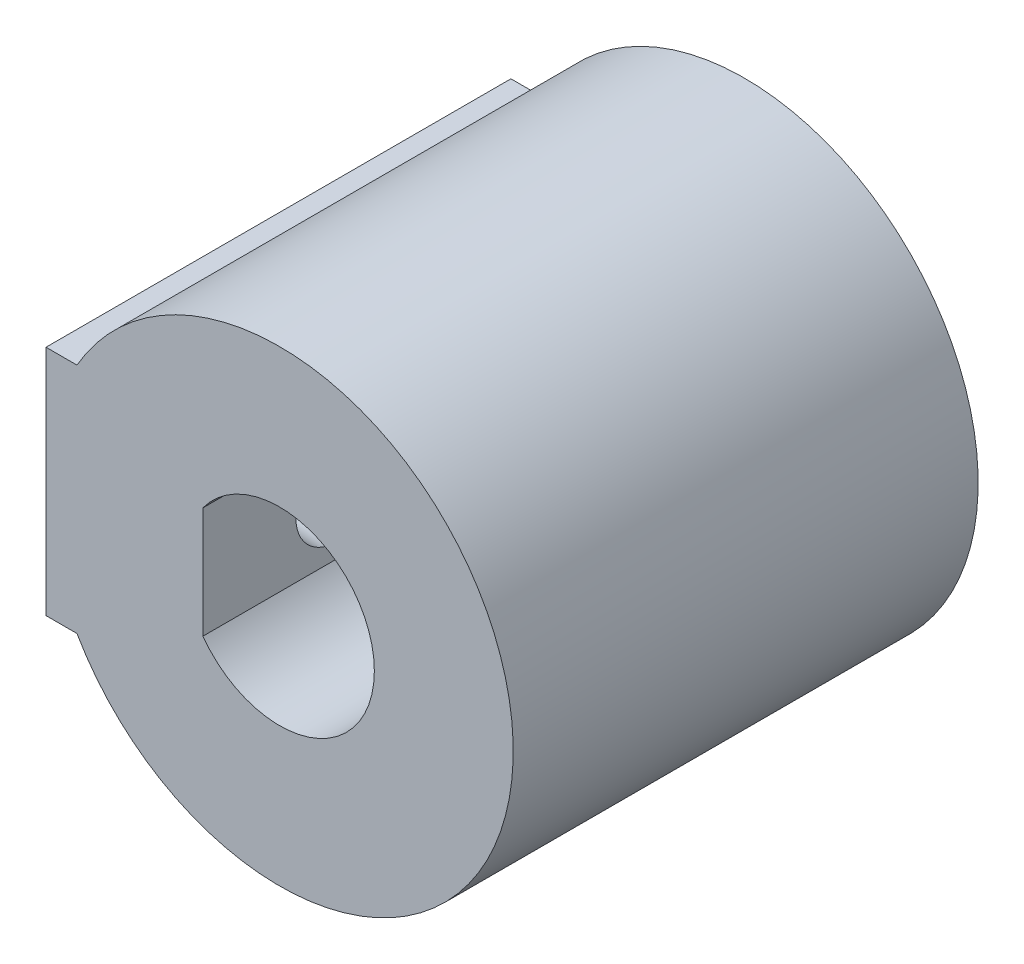
SolidWorks part; units mm, degrees
note: '?' marks a value the reader was unsure of.
ref_plane "Front Plane" through (0, 0, 0) normal (0, 0, 1) x (1, 0, 0)
ref_plane "Top Plane" through (0, 0, 0) normal (0, 1, 0) x (1, 0, 0)
ref_plane "Right Plane" through (0, 0, 0) normal (1, 0, 0) x (0, 0, -1)
sketch "Sketch1" plane through (0, 0, 0) normal (0, 0, 1) x (1, 0, 0)
  circle A0 centre (0, 0) radius 10.05
  dimension "D1" = 20.1
extrude "Boss-Extrude1" add sketch "Sketch1" along normal blind 20
ref_axis "Axis1" through (0, 0, 20) along (0, 0, -1)?
sketch "Sketch4" plane through (0, 0, 0) normal (0, 0, -1) x (-1, 0, 0)
  line L0 (-1.6, -2.1) -> (-1.6, 2.1)
  line L1 (1.6, 2.1) -> (1.6, -2.1)
  line L2 (-1.6, -2.1) -> (1.6, -2.1) construction
  line L3 (-1.6, 2.1) -> (1.6, 2.1) construction
  arc A0 (-1.6, 2.1) -> (1.6, 2.1) centre (0, -0.0749) cw
  arc A1 (1.6, -2.1) -> (-1.6, -2.1) centre (0, 0.0749) cw
  point P6 (-1.6, 0)
  point P7 (0, -2.1)
  point P8 (1.6, 0)
  point P10 (0, 2.1)
  dimension "D3" = 2.7
  dimension "D4" = 2.7
  dimension "D1" = 4.2
  dimension "D2" = 3.2
extrude "Cut-Extrude2" cut sketch "Sketch4" against normal blind 8.5
sketch "Sketch5" plane through (0, 0, 0) normal (0, 0, -1) x (-1, 0, 0)
  circle A1 centre (0, 0) radius 2.6401
  arc A2 (1.6, 2.1) -> (-1.6, 2.1) centre (0, -0.0749) ccw construction
  arc A3 (1.6, 2.1) -> (-1.6, 2.1) centre (0, -0.0749) ccw
  arc A4 (-1.6, -2.1) -> (1.6, -2.1) centre (0, 0.0749) ccw construction
  arc A5 (-1.6, -2.1) -> (1.6, -2.1) centre (0, 0.0749) ccw construction
extrude "Cut-Extrude3" cut sketch "Sketch5" against normal blind 3
sketch "Sketch3" plane through (0, 0, 20) normal (0, 0, 1) x (1, 0, 0)
  line L0 (-3.3, 2.3907) -> (-3.3, -2.3907)
  circle A0 centre (0, 0) radius 4.075
  dimension "D1" = 8.15
  dimension "D2" = 3.3
extrude "Cut-Extrude1" cut sketch "Sketch3" against normal up to surface (11.5 mm away) contours L0 A0 up to face at (0, 0, 8.5)
ref_plane "Plane1" through (-10.05, 0, 0) normal (-1, 0, 0) x (0, 0, 1)
sketch "Sketch8" plane through (-10.05, 0, 0) normal (-1, 0, 0) x (0, 0, 1)
  line L0 (0, 5) -> (20, 5)
  line L1 (0, 10.05) -> (0, -10.05) construction
  line L2 (20, -10.05) -> (20, 10.05) construction
  line L3 (20, 5) -> (20, -5)
  line L4 (20, -5) -> (0, -5)
  line L5 (0, -5) -> (0, 5)
  line L6 (20, 0) -> (0, 0) construction
  point P6 (20, 0)
  dimension "D1" = 10
extrude "Boss-Extrude2" add sketch "Sketch8" against normal up to surface (1.3321 mm away) up to face at (10.05, 0, 20)
sketch "Sketch6" plane through (-10.05, 0, 0) normal (-1, 0, 0) x (0, 0, 1)
  line L0 (8.5, 2.1) -> (3, 2.1) construction
  line L1 (3, -2.1) -> (3, 2.1) construction
  line L2 (8.5, 2.1) -> (8.5, -2.1) construction
  line L3 (8.5, -2.1) -> (3, -2.1) construction
  line L4 (8.5, -2.1) -> (3, -2.1)
  line L5 (8.5, 2.1) -> (8.5, -2.1)
  line L6 (3, -2.1) -> (3, 2.1)
  line L7 (8.5, 2.1) -> (3, 2.1)
  circle A0 centre (5.75, 0) radius 1.75
  point P2 (5.75, 2.1)
  point P3 (3, 0)
  dimension "D1" = 3.5
extrude "Cut-Extrude4" cut sketch "Sketch6" against normal up to surface (8.45 mm away) contours A0 up to face at (-1.6, 0, 5.75)
sketch "Sketch7" plane through (-10.05, 0, 0) normal (-1, 0, 0) x (0, 0, 1)
  line L1 (8.5, -4.075) -> (8.5, 4.075) construction
  line L2 (8.5, -4.075) -> (8.5, 4.075)
  line L3 (20, -10.05) -> (20, 10.05) construction
  line L4 (20, -10.05) -> (20, 10.05)
  line L5 (8.5, 0) -> (20, 0) construction
  circle A0 centre (14.25, 0) radius 1.75
  point P3 (14.25, 0)
  dimension "D1" = 3.5
extrude "Cut-Extrude5" cut sketch "Sketch7" against normal up to surface (14.125 mm away) contours A0 L5 | L5 A0 up to face at (0.3875, 0, 14.25)
chamfer "Chamfer1" distance 0.5 angle 45 2 edges at (-10.05, 0, 16) (-10.05, 0, 7.5)
